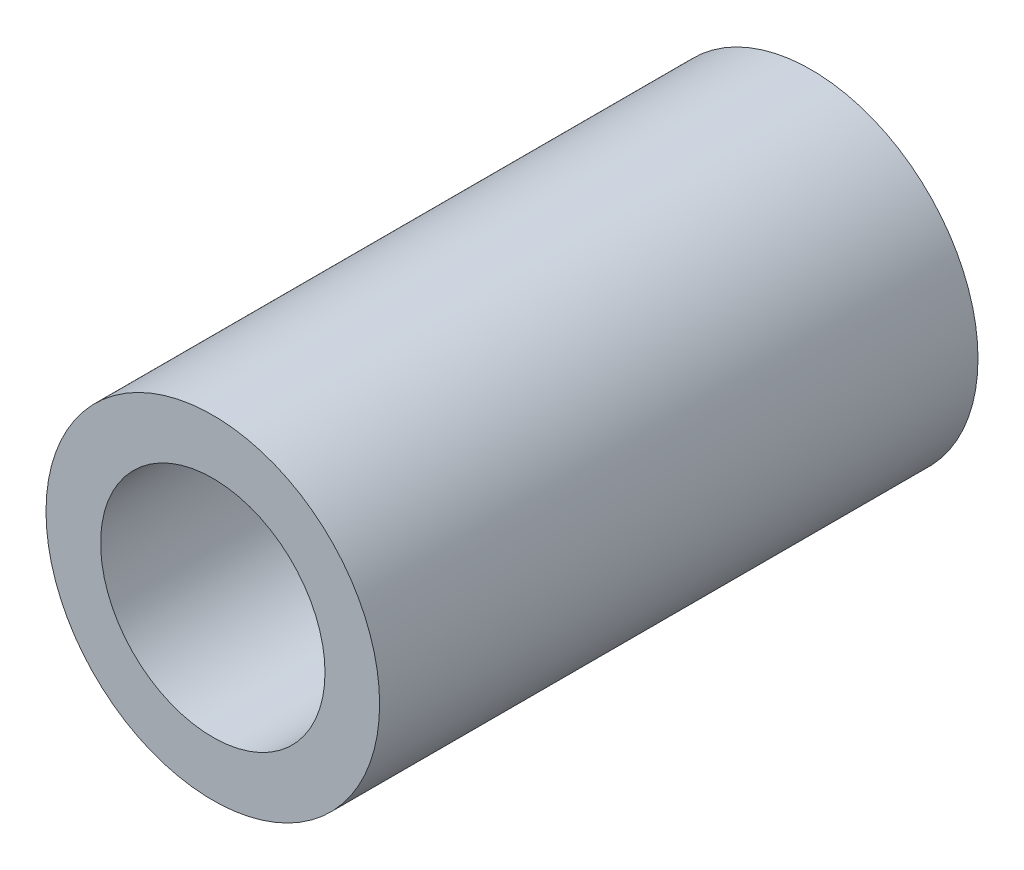
SolidWorks part; units mm, degrees
material "Tungsten"
ref_plane "Front Plane" through (0, 0, 0) normal (0, 0, 1) x (1, 0, 0)
ref_plane "Top Plane" through (0, 0, 0) normal (0, 1, 0) x (1, 0, 0)
ref_plane "Right Plane" through (0, 0, 0) normal (1, 0, 0) x (0, 0, -1)
sketch "Sketch1" plane through (0, 0, 0) normal (0, 0, 1) x (1, 0, 0)
  circle A0 centre (0, 0) radius 9.525
  circle A1 centre (0, 0) radius 14.1605
  dimension "D1" = 19.05
  dimension "D2" = 28.321
extrude "Boss-Extrude1" add sketch "Sketch1" along normal mid plane 50.8
ref_point "Point1"
